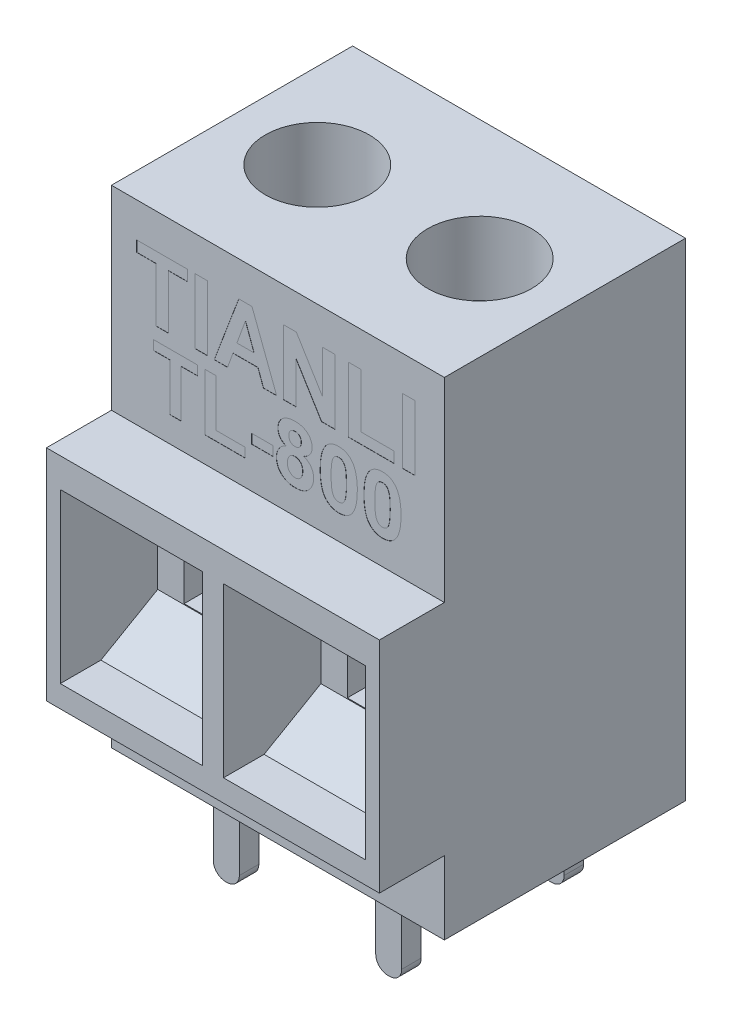
SolidWorks part; units mm, degrees
ref_plane "Front Plane" through (0, 0, 0) normal (0, 0, 1) x (1, 0, 0)
ref_plane "Top Plane" through (0, 0, 0) normal (0, 1, 0) x (1, 0, 0)
ref_plane "Right Plane" through (0, 0, 0) normal (1, 0, 0) x (0, 0, -1)
sketch "Sketch1" plane through (0, 0, 0) normal (1, 0, 0) x (0, 0, -1)
  line L0 (0, 66.3882) -> (0, -65.5147) construction
  line L1 (7.425, 15) -> (-7.425, 15)
  line L2 (-7.425, 15) -> (-7.425, 3)
  line L3 (-7.425, 3) -> (-11.425, 3)
  line L4 (-11.425, 3) -> (-11.425, -10.5)
  line L5 (-11.425, -10.5) -> (-7.425, -10.5)
  line L6 (-7.425, -10.5) -> (-7.425, -15)
  line L7 (-7.425, -15) -> (7.425, -15)
  line L8 (7.425, -15) -> (7.425, 15)
  point P5 (0, -65.5147)
  point P12 (0, 66.3882)
  point P13 (-6.1478, 3.3163)
  point P14 (-6.9448, -29.5223)
  point P15 (0, 15)
  point P16 (7.425, 0)
  dimension "D1" = 14.85
  dimension "D2" = 30
  dimension "D3" = 12
  dimension "D4" = 4
  dimension "D5" = 4.5
extrude "Boss-Extrude1" add sketch "Sketch1" along normal mid plane 20.5
sketch "Sketch2" plane through (0, 0, 11.425) normal (0, 0, 1) x (1, 0, 0)
  line L0 (0, 6.6704) -> (0, -3.1764) construction
  line L1 (9.4, -9.15) -> (0.65, -9.15)
  line L2 (-9.4, 1.2) -> (-0.65, 1.2)
  line L3 (-9.4, 1.2) -> (-9.4, -9.15)
  line L4 (-9.4, -9.15) -> (-0.65, -9.15)
  line L5 (-0.65, 1.2) -> (-0.65, -9.15)
  line L6 (-9.4, 1.2) -> (-0.65, -9.15) construction
  line L7 (-9.4, -9.15) -> (-0.65, 1.2) construction
  line L8 (0.65, 1.2) -> (0.65, -9.15)
  line L9 (9.4, 1.2) -> (0.65, 1.2)
  line L10 (9.4, 1.2) -> (9.4, -9.15)
  line L11 (10.25, -10.5) -> (-10.25, -10.5) construction
  point P3 (-5.025, -3.975)
  dimension "D1" = 8.75
  dimension "D2" = 10.35
  dimension "D3" = 1.35
  dimension "D4" = 1.3
extrude "Cut-Extrude1" cut sketch "Sketch2" against normal blind 6
sketch "Sketch4" plane through (0, 0, 5.425) normal (0, 0, 1) x (1, 0, 0)
  line L0 (-0.65, -9.15) -> (-0.65, 1.2) construction
  line L1 (-2.275, -0.875) -> (-7.775, -0.875)
  line L2 (-2.275, -0.875) -> (-2.275, -7.075)
  line L3 (-2.275, -7.075) -> (-7.775, -7.075)
  line L4 (-7.775, -0.875) -> (-7.775, -7.075)
  line L5 (-2.275, -0.875) -> (-7.775, -7.075) construction
  line L6 (-2.275, -7.075) -> (-7.775, -0.875) construction
  line L7 (-0.65, 1.2) -> (-9.4, 1.2) construction
  line L8 (0, 0) -> (0, 5.9557) construction
  line L9 (2.275, -7.075) -> (7.775, -7.075)
  line L10 (7.775, -0.875) -> (7.775, -7.075)
  line L11 (2.275, -0.875) -> (7.775, -0.875)
  line L12 (2.275, -0.875) -> (2.275, -7.075)
  point P0 (-5.025, -3.975)
  point P7 (-0.65, -3.975)
  point P10 (-5.025, 1.2)
  dimension "D1" = 6.2
  dimension "D2" = 5.5
extrude "Cut-Extrude2" cut sketch "Sketch4" against normal blind 6
chamfer "Chamfer1" distance 3.5 angle 30 4 edges at (5.025, -9.15, 5.425) (5.025, 1.2, 5.425) (-5.025, 1.2, 5.425) (-5.025, -9.15, 5.425) first distance on face at (5.025, -9.15, 8.425) first distance on face at (5.025, 1.2, 8.425) first distance on face at (-5.025, 1.2, 8.425) first distance on face at (-5.025, -9.15, 8.425)
sketch "Sketch5" plane through (0, 15, 0) normal (0, 1, 0) x (1, 0, 0)
  line L0 (0, 0) -> (-10.25, 0) construction
  line L1 (0, 0) -> (0, -7.425) construction
  line L2 (-10.25, 7.425) -> (-10.25, -7.425) construction
  line L3 (10.25, -7.425) -> (-10.25, -7.425) construction
  circle A0 centre (-5, 0) radius 3.2
  circle A1 centre (5, 0) radius 3.2
  dimension "D1" = 6.4
  dimension "D2" = 10
extrude "Cut-Extrude3" cut sketch "Sketch5" against normal blind 4.5
sketch "Sketch6" plane through (0, 10.5, 0) normal (0, 1, 0) x (1, 0, 0)
  line L0 (-7.2223, 0) -> (-2.7777, 0)
  line L1 (-5, -1.75) -> (-5, 1.75)
  line L2 (0, 0) -> (0, -2.7983) construction
  line L3 (5, -1.75) -> (5, 1.75)
  line L4 (7.2223, 0) -> (2.7777, 0)
  line L5 (-5, 3.2) -> (-5, -3.2) construction
  circle A2 centre (-5, 0) radius 3.2 construction
  circle A3 centre (-5, 0) radius 3.2 construction
  point P2 (-5, 3.2)
  point P3 (-5, 3.2)
  point P10 (-5, 0)
  dimension "D1" = 3.5
  dimension "D2" = 5
extrude "Cut-Extrude-Thin1" cut sketch "Sketch6" against normal blind 1.5 thin thin type mid plane wall 1
sketch "Sketch7" plane through (0, -15, 0) normal (0, -1, 0) x (1, 0, 0)
  line L0 (0, 14.2864) -> (0, -10.6744) construction
  line L1 (-13.0408, 0) -> (12.0493, 0) construction
  line L2 (-4.2, 4.4) -> (-5.8, 4.4)
  line L3 (4.2, 5.6) -> (5.8, 5.6)
  line L4 (4.2, 5.6) -> (4.2, 4.4)
  line L5 (4.2, 4.4) -> (5.8, 4.4)
  line L6 (5.8, 5.6) -> (5.8, 4.4)
  line L7 (4.2, 5.6) -> (5.8, 4.4) construction
  line L8 (4.2, 4.4) -> (5.8, 5.6) construction
  line L9 (-5.8, 5.6) -> (-5.8, 4.4)
  line L10 (-4.2, 5.6) -> (-5.8, 5.6)
  line L11 (-4.2, 5.6) -> (-4.2, 4.4)
  line L12 (-4.2, -5.6) -> (-4.2, -4.4)
  line L13 (-4.2, -5.6) -> (-5.8, -5.6)
  line L14 (-5.8, -5.6) -> (-5.8, -4.4)
  line L15 (-4.2, -4.4) -> (-5.8, -4.4)
  line L16 (4.2, -4.4) -> (5.8, -4.4)
  line L17 (5.8, -5.6) -> (5.8, -4.4)
  line L18 (4.2, -5.6) -> (5.8, -5.6)
  line L19 (4.2, -5.6) -> (4.2, -4.4)
  point P9 (5, 5)
  dimension "D1" = 10
  dimension "D2" = 10
  dimension "D3" = 1.6
  dimension "D4" = 1.2
extrude "Boss-Extrude2" add sketch "Sketch7" along normal blind 5.45
fillet "Fillet1" radius 0.75 8 edges at (4.2, -20.45, -5) (5.8, -20.45, -5) (-4.2, -20.45, -5) (-5.8, -20.45, -5) (-5.8, -20.45, 5) (-4.2, -20.45, 5) (4.2, -20.45, 5) (5.8, -20.45, 5)
sketch "Sketch8" plane through (0, 0, 7.425) normal (0, 0, 1) x (1, 0, 0)
  line L0 (-10.25, 8.8613) -> (10.25, 8.8613) construction
  line L1 (-10.25, 4.5647) -> (10.25, 4.5647) construction
  line L2 (10.25, 15) -> (10.25, 3) construction
  text T0 "TIANLI" font "Arial" height 4
  text T1 "TL-800" font "Arial" height 3.5
  point P4 (0, 8.8613)
  point P5 (0, 4.5647)
  point P7 (10.25, 4.5647)
  point P10 (10.25, 10.4645)
extrude "Cut-Extrude4" cut sketch "Sketch8" against normal blind 0.01
